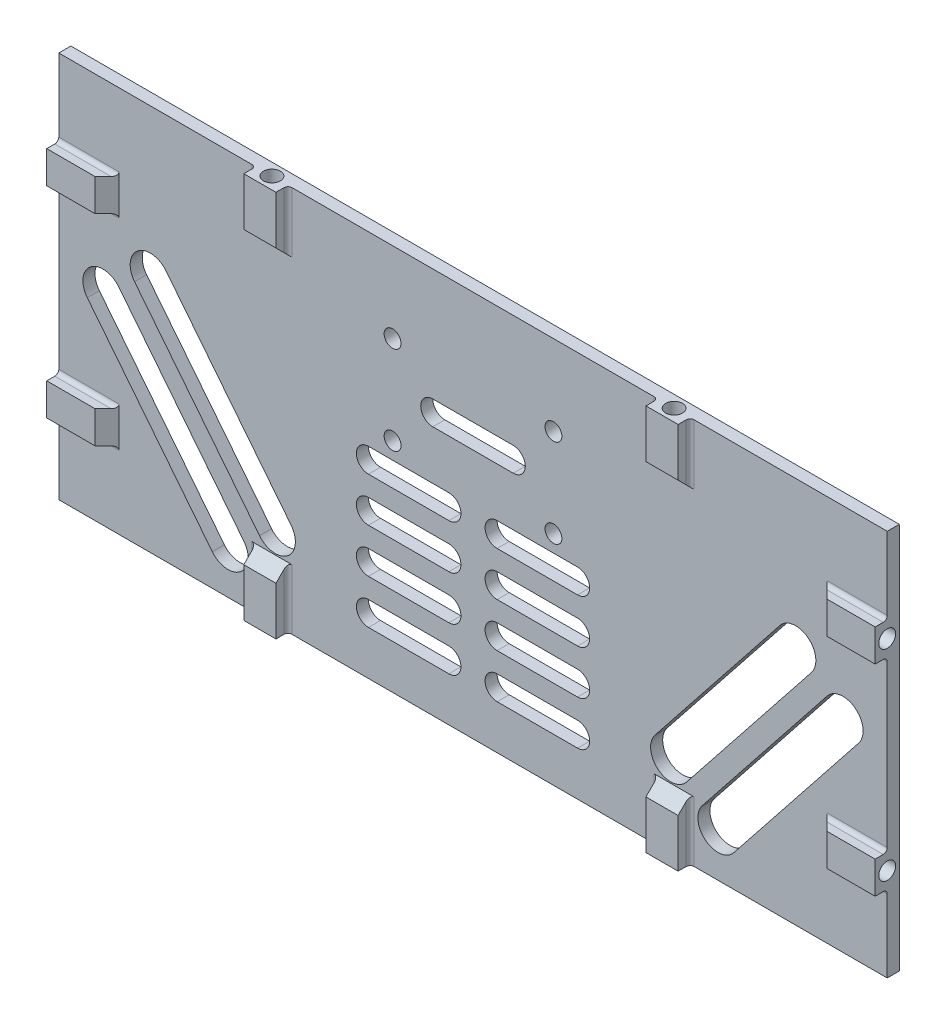
SolidWorks part; units mm, degrees
ref_plane "Front Plane" through (0, 0, 0) normal (1, 0, 0) x (0, 1, 0)
ref_plane "Top Plane" through (0, 0, 0) normal (0, 0, 1) x (0, 1, 0)
ref_plane "Right Plane" through (0, 0, 0) normal (0, 1, 0) x (-1, 0, 0)
sketch "Sketch1" plane through (0, 0, 0) normal (0, 0, 1) x (0, 1, 0)
  line L0 (11, 163.9146) -> (50.1625, 195) construction
  line L1 (0, 0) -> (96.2019, 0)
  line L2 (0, 0) -> (0, 206)
  line L3 (0, 206) -> (96.2019, 206)
  line L4 (96.2019, 0) -> (96.2019, 206)
  line L5 (7.8915, 167.8308) -> (47.0539, 198.9162)
  line L6 (14.1085, 159.9983) -> (53.271, 191.0838)
  line L7 (20.3256, 152.1659) -> (59.4881, 183.2513) construction
  line L8 (17.2171, 156.0821) -> (56.3795, 187.1675)
  line L9 (23.4342, 148.2496) -> (62.5966, 179.335)
  line L10 (20.3256, 53.8341) -> (59.4881, 22.7487) construction
  line L11 (23.4342, 57.7504) -> (62.5966, 26.665)
  line L12 (17.2171, 49.9179) -> (56.3795, 18.8325)
  line L13 (11, 42.0854) -> (50.1625, 11) construction
  line L14 (14.1085, 46.0017) -> (53.271, 14.9162)
  line L15 (7.8915, 38.1692) -> (47.0539, 7.0838)
  line L16 (6, 200) -> (90.2019, 200) construction
  line L17 (90.2019, 6) -> (90.2019, 200) construction
  line L18 (6, 6) -> (90.2019, 6) construction
  line L19 (6, 6) -> (6, 200) construction
  line L20 (55.8833, 147.5809) -> (78.9144, 118.5655) construction
  line L21 (65.5213, 70.5614) -> (46.6427, 46.7775) construction
  line L22 (96.2019, 103) -> (0, 103) construction
  line L23 (14, 129) -> (14, 109) construction
  line L24 (17, 129) -> (17, 109)
  line L25 (11, 129) -> (11, 109)
  line L26 (25, 129) -> (25, 109) construction
  line L27 (28, 129) -> (28, 109)
  line L28 (22, 129) -> (22, 109)
  line L29 (36, 129) -> (36, 109) construction
  line L30 (39, 129) -> (39, 109)
  line L31 (33, 129) -> (33, 109)
  line L32 (47, 129) -> (47, 109) construction
  line L33 (50, 129) -> (50, 109)
  line L34 (44, 129) -> (44, 109)
  line L41 (14, 77) -> (14, 97) construction
  line L42 (17, 77) -> (17, 97)
  line L43 (11, 77) -> (11, 97)
  line L44 (25, 77) -> (25, 97) construction
  line L45 (28, 77) -> (28, 97)
  line L46 (22, 77) -> (22, 97)
  line L47 (36, 77) -> (36, 97) construction
  line L48 (39, 77) -> (39, 97)
  line L49 (33, 77) -> (33, 97)
  line L50 (47, 77) -> (47, 97) construction
  line L51 (50, 77) -> (50, 97)
  line L52 (44, 77) -> (44, 97)
  line L53 (54.2019, 83) -> (76.2019, 83) construction
  line L56 (54.2019, 83) -> (54.2019, 123) construction
  line L59 (65.2019, 113) -> (65.2019, 93) construction
  line L60 (68.2019, 113) -> (68.2019, 93)
  line L61 (62.2019, 113) -> (62.2019, 93)
  line L67 (54.2019, 123) -> (76.2019, 123) construction
  line L68 (76.2019, 83) -> (76.2019, 123) construction
  line L69 (54.2019, 83) -> (76.2019, 123) construction
  line L70 (54.2019, 123) -> (76.2019, 83) construction
  line L263 (69, 66) -> (69, 46) construction
  line L264 (72, 66) -> (72, 46)
  line L265 (66, 66) -> (66, 46)
  line L266 (58, 66) -> (58, 46) construction
  line L267 (61, 66) -> (61, 46)
  line L268 (55, 66) -> (55, 46)
  line L269 (69, 129) -> (69, 109) construction
  line L270 (72, 129) -> (72, 109)
  line L271 (66, 129) -> (66, 109)
  line L272 (58, 129) -> (58, 109) construction
  line L273 (61, 129) -> (61, 109)
  line L274 (55, 129) -> (55, 109)
  arc A0 (7.8915, 167.8308) -> (14.1085, 159.9983) centre (11, 163.9146) ccw
  arc A1 (53.271, 191.0838) -> (47.0539, 198.9162) centre (50.1625, 195) ccw
  arc A2 (17.2171, 156.0821) -> (23.4342, 148.2496) centre (20.3256, 152.1659) ccw
  arc A3 (62.5966, 179.335) -> (56.3795, 187.1675) centre (59.4881, 183.2513) ccw
  arc A4 (23.4342, 57.7504) -> (17.2171, 49.9179) centre (20.3256, 53.8341) ccw
  arc A5 (56.3795, 18.8325) -> (62.5966, 26.665) centre (59.4881, 22.7487) ccw
  arc A6 (14.1085, 46.0017) -> (7.8915, 38.1692) centre (11, 42.0854) ccw
  arc A7 (47.0539, 7.0838) -> (53.271, 14.9162) centre (50.1625, 11) ccw
  circle A9 centre (76.2019, 123) radius 2.1
  circle A11 centre (76.2019, 83) radius 2.1
  arc A12 (17, 129) -> (11, 129) centre (14, 129) ccw
  arc A13 (11, 109) -> (17, 109) centre (14, 109) ccw
  arc A14 (28, 129) -> (22, 129) centre (25, 129) ccw
  arc A15 (22, 109) -> (28, 109) centre (25, 109) ccw
  arc A16 (39, 129) -> (33, 129) centre (36, 129) ccw
  arc A17 (33, 109) -> (39, 109) centre (36, 109) ccw
  arc A18 (50, 129) -> (44, 129) centre (47, 129) ccw
  arc A19 (44, 109) -> (50, 109) centre (47, 109) ccw
  arc A24 (17, 77) -> (11, 77) centre (14, 77) cw
  arc A25 (11, 97) -> (17, 97) centre (14, 97) cw
  arc A26 (28, 77) -> (22, 77) centre (25, 77) cw
  arc A27 (22, 97) -> (28, 97) centre (25, 97) cw
  arc A28 (39, 77) -> (33, 77) centre (36, 77) cw
  arc A29 (33, 97) -> (39, 97) centre (36, 97) cw
  arc A30 (50, 77) -> (44, 77) centre (47, 77) cw
  arc A31 (44, 97) -> (50, 97) centre (47, 97) cw
  arc A36 (68.2019, 113) -> (62.2019, 113) centre (65.2019, 113) ccw
  arc A37 (62.2019, 93) -> (68.2019, 93) centre (65.2019, 93) ccw
  circle A42 centre (54.2019, 123) radius 2.1
  circle A43 centre (54.2019, 83) radius 2.1
  arc A176 (72, 129) -> (66, 129) centre (69, 129) ccw
  arc A177 (66, 109) -> (72, 109) centre (69, 109) ccw
  arc A178 (61, 129) -> (55, 129) centre (58, 129) ccw
  arc A179 (55, 109) -> (61, 109) centre (58, 109) ccw
  point P7 (30.5812, 179.4573)
  point P12 (39.9068, 167.7086)
  point P19 (39.9068, 38.2914)
  point P26 (30.5812, 26.5427)
  point P40 (65.2019, 103)
  point P42 (65.2019, 103)
  point P54 (14, 119)
  point P59 (65.2019, 103)
  point P63 (25, 119)
  point P70 (36, 119)
  point P77 (47, 119)
  point P84 (69, 119)
  point P94 (91.2696, 103)
  point P97 (14, 87)
  point P104 (25, 87)
  point P111 (36, 87)
  point P118 (47, 87)
  point P146 (58, 119)
  point P153 (69, 119)
  point P160 (58, 119)
  point P167 (69, 119)
  point P174 (58, 119)
  point P181 (69, 119)
  point P188 (58, 119)
  point P195 (69, 119)
  point P202 (58, 119)
  point P209 (69, 119)
  point P216 (58, 119)
  point P223 (69, 119)
  point P230 (58, 119)
  point P237 (69, 119)
  point P244 (58, 119)
  point P251 (69, 119)
  point P258 (58, 119)
  point P265 (69, 119)
  point P272 (58, 119)
  point P279 (69, 119)
  point P286 (58, 119)
  point P293 (69, 119)
  point P300 (58, 119)
  point P307 (69, 119)
  point P314 (58, 119)
  point P321 (69, 119)
  point P328 (58, 119)
  point P335 (69, 119)
  point P342 (58, 119)
  point P349 (69, 119)
  point P356 (58, 119)
  point P363 (69, 119)
  point P370 (58, 119)
  point P377 (69, 119)
  point P384 (58, 119)
  point P391 (69, 119)
  point P398 (58, 119)
  point P405 (69, 119)
  point P412 (58, 119)
  point P419 (69, 119)
  point P426 (58, 119)
  point P433 (69, 119)
  point P440 (58, 119)
  point P447 (69, 119)
  point P454 (58, 119)
  point P461 (69, 119)
  point P468 (58, 119)
  point P475 (69, 119)
  point P482 (58, 119)
  point P489 (69, 119)
  point P496 (58, 119)
  point P503 (69, 119)
  point P510 (58, 119)
  point P517 (69, 119)
  point P524 (58, 119)
  point P531 (69, 119)
  point P538 (58, 119)
  point P545 (69, 119)
  point P552 (58, 119)
  point P559 (69, 66)
  point P566 (58, 66)
  point P573 (69, 66)
  point P580 (58, 66)
  point P587 (69, 56)
  point P594 (58, 56)
  point P601 (69, 56)
  point P608 (58, 56)
  point P615 (69, 119)
  point P622 (58, 119)
  dimension "D9" = 4.2
  dimension "D1" = 96.2019
  dimension "D2" = 206
  dimension "D4" = 5
  dimension "D5" = 5
  dimension "D6" = 103.118
  dimension "D7" = 10
  dimension "D8" = 50
  dimension "D10" = 20
  dimension "D11" = 20
  dimension "D14" = 5
  dimension "D15" = 5
  dimension "D16" = 6
  dimension "20" = 20
  dimension "D17" = 6
  dimension "D18" = 20
  dimension "D19" = 6
  dimension "D12" = 22
  dimension "D3" = 6
  dimension "D13" = 6
extrude "Boss-Extrude1" add sketch "Sketch1" along normal blind 3
sketch "Sketch2" plane through (0, 0, 0) normal (0, -1, 0) x (1, 0, 0)
  line L0 (-153, 6) -> (-153, 0) construction
  line L1 (-157, 6) -> (-149, 6)
  line L2 (-53, 6) -> (-53, 0) construction
  line L5 (-103, 3) -> (-103, 0) construction
  line L6 (-206, 3) -> (0, 3) construction
  line L7 (-206, 0) -> (0, 0) construction
  line L8 (-157, 6) -> (-157, 0)
  line L9 (-157, 0) -> (-149, 0)
  line L10 (-149, 6) -> (-149, 0)
  line L11 (-57, 6) -> (-57, 0)
  line L12 (-49, 0) -> (-57, 0)
  line L13 (-49, 6) -> (-49, 0)
  line L14 (-49, 6) -> (-57, 6)
  circle A0 centre (-153, 3) radius 2.1
  circle A2 centre (-53, 3) radius 2.1
  dimension "D3" = 6
  dimension "D1" = 4.2
  dimension "D4" = 8
  dimension "D2" = 50
extrude "Boss-Extrude2" add sketch "Sketch2<3>" against normal blind 12 contours L8 L9 L10 L1 | L14 L11 L12 L13
sketch "Sketch2<3>" plane through (0, 0, 0) normal (0, -1, 0) x (1, 0, 0) same geometry as "Sketch2"
extrude "Boss-Extrude3" add sketch "Sketch2<4>" along normal blind 12 from surface contours L14 L11 L12 L13 | L1 L10 L9 L8 starting at face at (-103, 96.2019, 1.5)
sketch "Sketch2<4>" plane through (0, 0, 0) normal (0, -1, 0) x (1, 0, 0) same geometry as "Sketch2"
sketch "Sketch3" plane through (0, 0, 0) normal (1, 0, 0) x (0, 1, 0)
  line L1 (23.1009, 6) -> (23.1009, 0) construction
  line L4 (0, 3) -> (96.2019, 3) construction
  line L5 (48.1009, 3) -> (48.1009, 0) construction
  line L6 (0, 0) -> (96.2019, 0) construction
  line L7 (19.1009, 0) -> (27.1009, 0)
  line L8 (19.1009, 0) -> (19.1009, 6)
  line L9 (19.1009, 6) -> (27.1009, 6)
  line L10 (27.1009, 0) -> (27.1009, 6)
  line L11 (77.1009, 0) -> (69.1009, 0)
  line L12 (69.1009, 0) -> (69.1009, 6)
  line L13 (77.1009, 6) -> (69.1009, 6)
  line L14 (77.1009, 0) -> (77.1009, 6)
  circle A0 centre (23.1009, 3) radius 2.1
  circle A2 centre (73.1009, 3) radius 2.1
  dimension "D3" = 6
  dimension "D1" = 4.2
  dimension "D4" = 8
  dimension "D2" = 25
extrude "Boss-Extrude4" add sketch "Sketch3<3>" against normal blind 12 contours L9 L10 L7 L8 | L13 L12 L11 L14
sketch "Sketch3<3>" plane through (0, 0, 0) normal (1, 0, 0) x (0, 1, 0) same geometry as "Sketch3"
extrude "Boss-Extrude5" add sketch "Sketch3<4>" along normal blind 12 from surface contours L9 L10 L7 L8 | L13 L12 L11 L14 starting at face at (-206, 48.1009, 1.5)
sketch "Sketch3<4>" plane through (0, 0, 0) normal (1, 0, 0) x (0, 1, 0) same geometry as "Sketch3"
extrude "Cut-Extrude1" cut sketch "Sketch2" against normal blind 10 contours A2 | A0
extrude "Cut-Extrude2" cut sketch "Sketch2<2>" along normal blind 10 from surface contours A2 | A0 starting at face at (-103, 96.2019, 3.5)
sketch "Sketch2<2>" plane through (0, 0, 0) normal (0, -1, 0) x (1, 0, 0) same geometry as "Sketch2"
extrude "Cut-Extrude3" cut sketch "Sketch3" against normal blind 10 contours A2 | A0
extrude "Cut-Extrude4" cut sketch "Sketch3<2>" along normal blind 10 from surface contours A2 | A0 starting at face at (-206, 48.1009, 3.5)
sketch "Sketch3<2>" plane through (0, 0, 0) normal (1, 0, 0) x (0, 1, 0) same geometry as "Sketch3"
chamfer "Chamfer1" distance 3 angle 45 8 edges at (-53, 84.2019, 3) (-153, 84.2019, 3) (-194, 73.1009, 3) (-194, 23.1009, 3) (-153, 12, 3) (-53, 12, 3) (-12, 23.1009, 3) (-12, 73.1009, 3)
fillet "Fillet1" radius 1 16 edges at (-149, 7.5, 3) (-157, 7.5, 3) (-198.5, 27.1009, 3) (-198.5, 19.1009, 3) (-198.5, 69.1009, 3) (-198.5, 77.1009, 3) (-157, 88.7019, 3) (-149, 88.7019, 3) (-7.5, 69.1009, 3) (-49, 88.7019, 3) (-57, 88.7019, 3) (-7.5, 77.1009, 3) (-57, 7.5, 3) (-49, 7.5, 3) (-7.5, 27.1009, 3) (-7.5, 19.1009, 3)
equation "\"MotorDriverLength\"= 60mm"
equation "\"MotorLength\"= 60"
equation "\"MotorDriverWidth\"=44"
equation "\"MotorWidth\"= 37"
equation "\"InnerWallThickness\"=3"
equation "\"BatteryWidth\"= 60"
equation "\"OuterWallThickness\" = 6"
equation "\"CompartmentHeight\"=37"
equation "\"CompartmentWidth\"= \"MotorDriverLength\""
equation "\"MotorDiameter\"=37"
equation "\"BatteryHeight\"=24.2019"
equation "\"MotorDriverHeight\"=28"
equation "\"CircuitHeight\"=30"
equation "\"FanThickness\"= 10"
equation "\"FanHeight\"=50"
equation "\"MotorShaftHole\"=12"
equation "\"BearingBore\"=10"
equation "\"MinShinWidth\"= 20"
equation "\"ShinThickness\"=10"
equation "\"PivotDistance\"=30"
equation "\"ThighLength\"= 150"
equation "\"KneeLength\" =80"
equation "\"HipBore\"=27"
equation "\"ThighThickness\"=10"
equation "\"MaxBending\"=135"
equation "\"MaxStretchingAngle\"= 50"
equation "\"ThighJointDistance\"=157.485"
equation "\"ShinLength\"=120"
equation "\"BearingDiameter\"= 10"
equation "\"CircuitLength\"=50"
equation "\"ChessisInnerWidth\"= \"OuterWallThickness\" * 2 + \"MotorDriverLength\" + \"MotorDiameter\" + \"InnerWallThickness\" * 3 + \"CircuitLength\""
equation "\"ChessisHeight\"= \"BatteryHeight\" + 10 + \"InnerWallThickness\" + \"MotorDiameter\" + 10 + \"OuterWallThickness\" * 2"
equation "\"D1@Sketch1\"=\"ChessisHeight\""
equation "\"ChassisWidth\"= \"MotorDriverWidth\"*4+30"
equation "\"D2@Sketch1\"=\"ChassisWidth\""
equation "\"D1@Boss-Extrude1\"=\"OuterWallThickness\""
equation "\"D3@Sketch2\"=\"OuterWallThickness\""
equation "\"D3@Sketch3\"=\"OuterWallThickness\""
